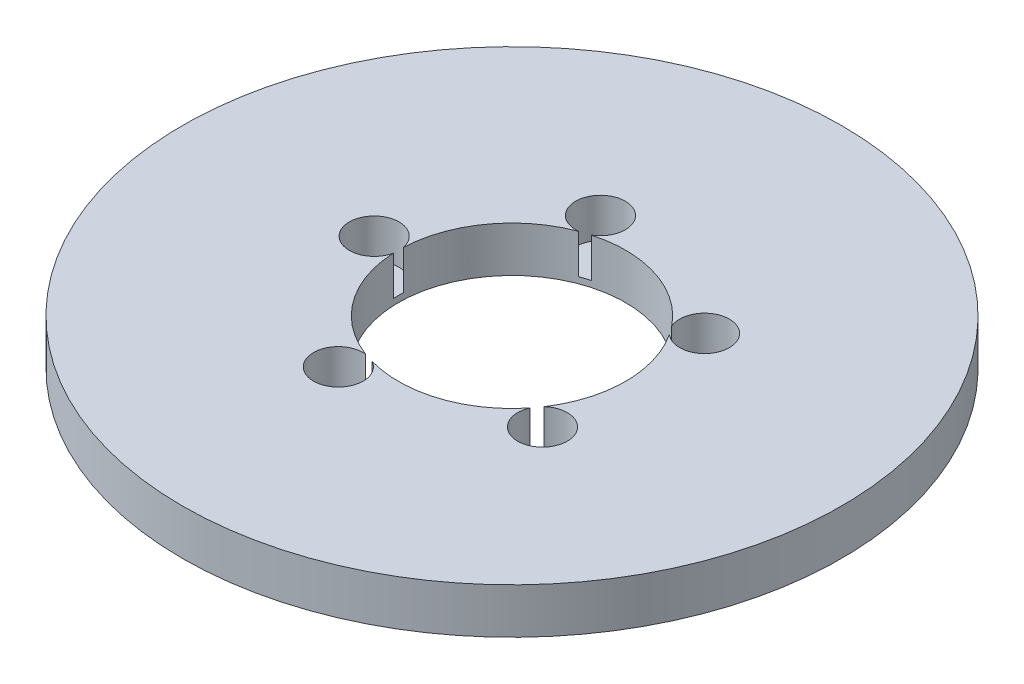
SolidWorks part; units mm, degrees
ref_plane "Front Plane" through (0, 0, 0) normal (0, 0, 1) x (1, 0, 0)
ref_plane "Top Plane" through (0, 0, 0) normal (0, 1, 0) x (1, 0, 0)
ref_plane "Right Plane" through (0, 0, 0) normal (1, 0, 0) x (0, 0, -1)
sketch "Sketch1" plane through (0, 0, 0) normal (0, 1, 0) x (1, 0, 0)
  circle A0 centre (0, 0) radius 72.5
  dimension "FLANGE_OD" = 145
extrude "Boss-Extrude1" add sketch "Sketch1" along normal blind 10
sketch "Sketch2" plane through (0, 0, 0) normal (0, 1, 0) x (1, 0, 0)
  circle A0 centre (0, 0) radius 25
  dimension "BORE_D" = 50
extrude "Cut-Extrude1" cut sketch "Sketch2" along normal through all
sketch "Sketch3" plane through (0, 10, 0) normal (0, 1, 0) x (1, 0, 0)
  circle A0 centre (0, 0) radius 30.3191 construction
  circle A1 centre (-30.3191, 0) radius 5.459
  dimension "BOLT_D" = 10.9181
  dimension "BOLT_PCD" = 60.6383
extrude "Cut-Extrude2" cut sketch "Sketch3" against normal blind 8.6454
pattern_circular "CirPattern1" count 5 over 360 about axis through (0, 0, 0) along (0, 1, 0) of "Cut-Extrude2"
